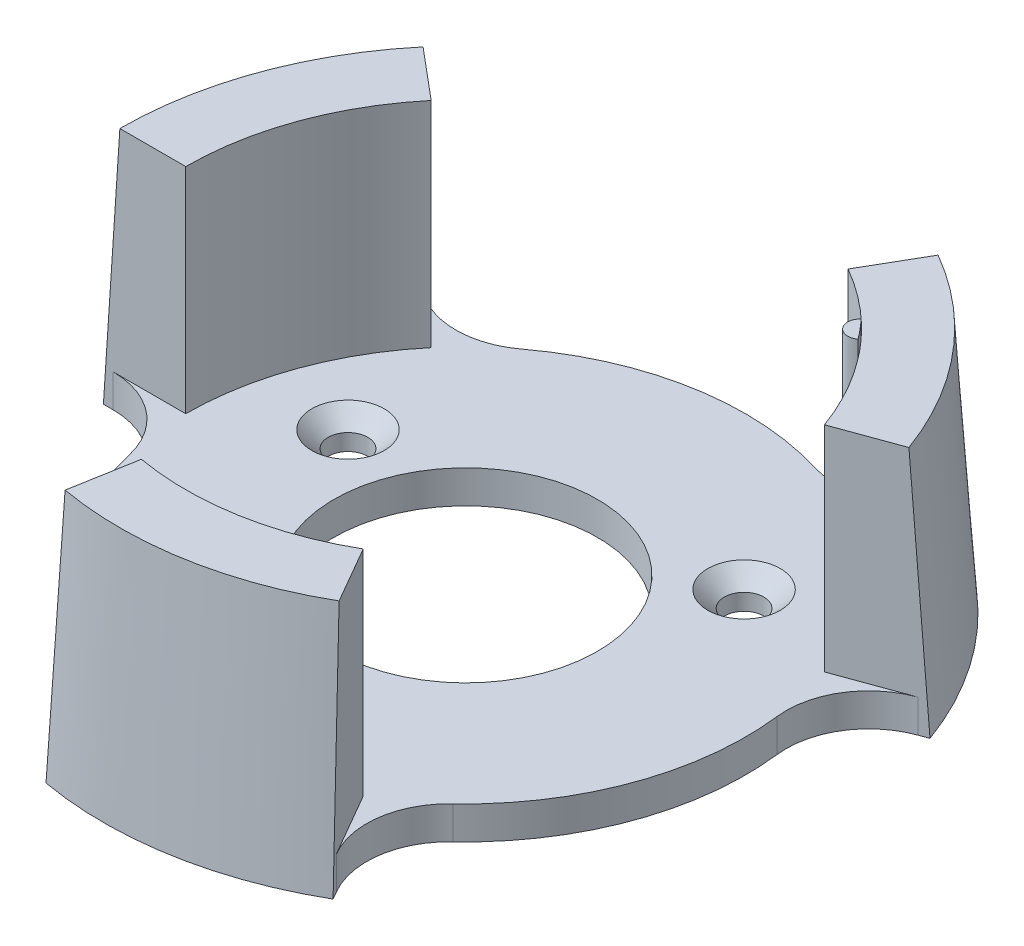
SolidWorks part; units mm, degrees
ref_plane "Front Plane" through (0, 0, 0) normal (0, 0, 1) x (1, 0, 0)
ref_plane "Top Plane" through (0, 0, 0) normal (0, 1, 0) x (1, 0, 0)
ref_plane "Right Plane" through (0, 0, 0) normal (1, 0, 0) x (0, 0, -1)
sketch "Sketch1" plane through (0, 0, 0) normal (0, 1, 0) x (1, 0, 0)
  circle A0 centre (0, 0) radius 8
  circle A1 centre (0, 0) radius 17
  dimension "D1" = 16
  dimension "D2" = 34
extrude "Boss-Extrude4" add sketch "Sketch1" along normal blind 2 contours A1 | A0
sketch "Sketch5" plane through (0, 0, 0) normal (0, 0, 1) x (1, 0, 0)
  line L0 (-17, 0) -> (-22, 0)
  line L1 (-17, 0) -> (-17, 15)
  line L2 (-17, 15) -> (-21, 15)
  line L3 (-21, 15) -> (-22, 0)
  line L4 (-17, 0) -> (17, 0) construction
  line L5 (0, 9.8137) -> (0, -8.5535) construction
  dimension "D1" = 15
  dimension "D2" = 5
  dimension "D3" = 4
revolve "Revolve2" add sketch "Sketch5" angle 40 about L5
pattern_circular "CirPattern1" count 3 over 360 about axis through (0, 2, 0) along (0, 1, 0) of "Revolve2"
fillet "Fillet1" radius 5 6 edges at (8.5, 1, 14.7224) (15.9748, 1, -5.8143) (8.5, 1, -14.7224) (-13.0228, 1, -10.9274) (-17, 1, 0) (-2.952, 1, 16.7417)
sketch "Sketch6" plane through (0, 2, 0) normal (0, 1, 0) x (1, 0, 0)
  line L0 (-15.9748, 5.8143) -> (20.5236, -7.47) construction
  line L1 (13.0228, 10.9274) -> (-17.0854, -14.3363) construction
  line L2 (2.952, -16.7417) -> (-4.6806, 26.545) construction
  arc A0 (-13.0228, 10.9274) -> (-17, 0) centre (0, 0) ccw construction
  arc A1 (15.9748, 5.8143) -> (8.5, 14.7224) centre (0, 0) ccw construction
  arc A2 (-2.952, -16.7417) -> (8.5, -14.7224) centre (0, 0) ccw construction
  circle A3 centre (0, 0) radius 12 construction
  point P19 (-11.2361, 4.0896)
  point P20 (2.0838, -11.8177)
  point P22 (0.0402, -0.0146)
  point P23 (9.1925, 7.7135)
  dimension "D1" = 24
hole_wizard "CSK for M2 Countersunk Flat Head Screw1" positions "Sketch12" profile "Sketch13" countersink size "M2" standard "ISO" end condition through all
sketch "Sketch12" plane through (0, 2, 0) normal (0, 1, 0) x (1, 0, 0)
  point P0 (2.0838, -11.8177)
  point P3 (9.1925, 7.7135)
  point P6 (-11.2361, 4.0896)
sketch "Sketch13" plane through (2.0838, 2, 11.8177) normal (1, 0, 0) x (0, 0, 1)
  line L0 (0, 0) -> (0, 2)
  line L1 (0, 2) -> (1.2, 2)
  line L2 (1.2, 2) -> (1.2, 1)
  line L3 (1.2, 1) -> (2.2, 0)
  line L5 (2.2, 0) -> (0, 0)
  line L6 (-1.2, 1) -> (-2.2, 0) construction
  line L11 (0, -6.35) -> (0, 107.95) construction
  dimension "Thru Hole Dia." = 2.4
  dimension "Thru Hole Depth" = 2
  dimension "Near C'Sink Dia." = 4.4
  dimension "Near C'Sink Angle" = 90
sketch "Sketch18" plane through (0, 0, 0) normal (0, -1, 0) x (1, 0, 0)
  line L0 (13.0228, -10.9274) -> (-17.0854, 14.3363) construction
sketch "Sketch22" plane through (0, 15, 0) normal (0, 1, 0) x (1, 0, 0)
  line L0 (2.952, -16.7417) -> (3.6466, -20.681) construction
  arc A0 (-2.952, -16.7417) -> (8.5, -14.7224) centre (0, 0) ccw construction
  arc A1 (-3.6466, -20.681) -> (10.5, -18.1865) centre (0, 0) ccw construction
sketch "Sketch24" plane through (0, 2, 0) normal (0, 1, 0) x (1, 0, 0)
  arc A0 (12.5281, 11.4912) -> (13.4921, 10.3423) centre (13.0228, 10.9274) ccw
  arc A1 (15.9748, 5.8143) -> (8.5, 14.7224) centre (0, 0) ccw construction
  arc A2 (13.4921, 10.3423) -> (12.5281, 11.4912) centre (0, 0) ccw
extrude "Boss-Extrude6" add sketch "Sketch24" along normal blind 14
